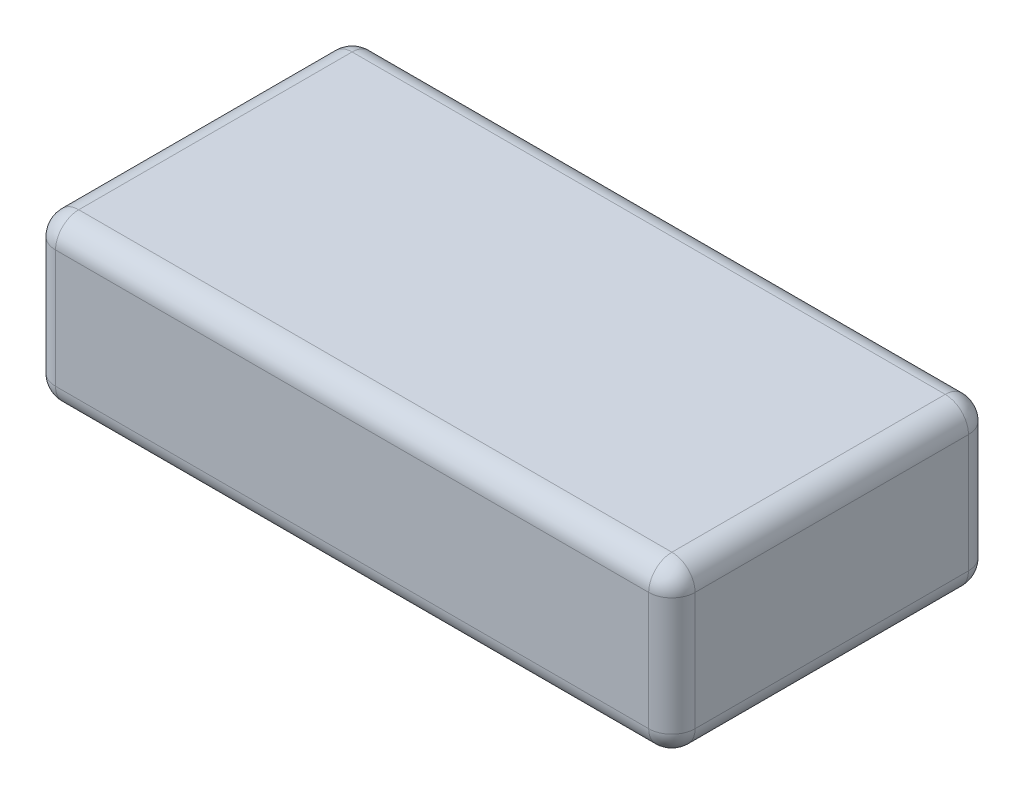
SolidWorks part; units mm, degrees
ref_plane "Front Plane" through (0, 0, 0) normal (0, 0, 1) x (1, 0, 0)
ref_plane "Top Plane" through (0, 0, 0) normal (0, 1, 0) x (1, 0, 0)
ref_plane "Right Plane" through (0, 0, 0) normal (1, 0, 0) x (0, 0, -1)
sketch "Sketch1" plane through (0, 0, 0) normal (0, 1, 0) x (1, 0, 0)
  line L1 (-26.6751, 23.1598) -> (43.3249, 23.1598)
  line L2 (-26.6751, 23.1598) -> (-26.6751, -11.8402)
  line L3 (-26.6751, -11.8402) -> (43.3249, -11.8402)
  line L4 (43.3249, 23.1598) -> (43.3249, -11.8402)
  dimension "D1" = 70
  dimension "D2" = 35
extrude "Boss-Extrude1" add sketch "Sketch1" along normal blind 18
fillet "Fillet1" radius 2.54 12 edges at (43.3249, 9, 11.8402) (8.3249, 0, 11.8402) (43.3249, 0, -5.6598) (-26.6751, 9, 11.8402) (-26.6751, 0, -5.6598) (43.3249, 9, -23.1598) (-26.6751, 9, -23.1598) (8.3249, 0, -23.1598) (8.3249, 18, -23.1598) (43.3249, 18, -5.6598) (8.3249, 18, 11.8402) (-26.6751, 18, -5.6598)
